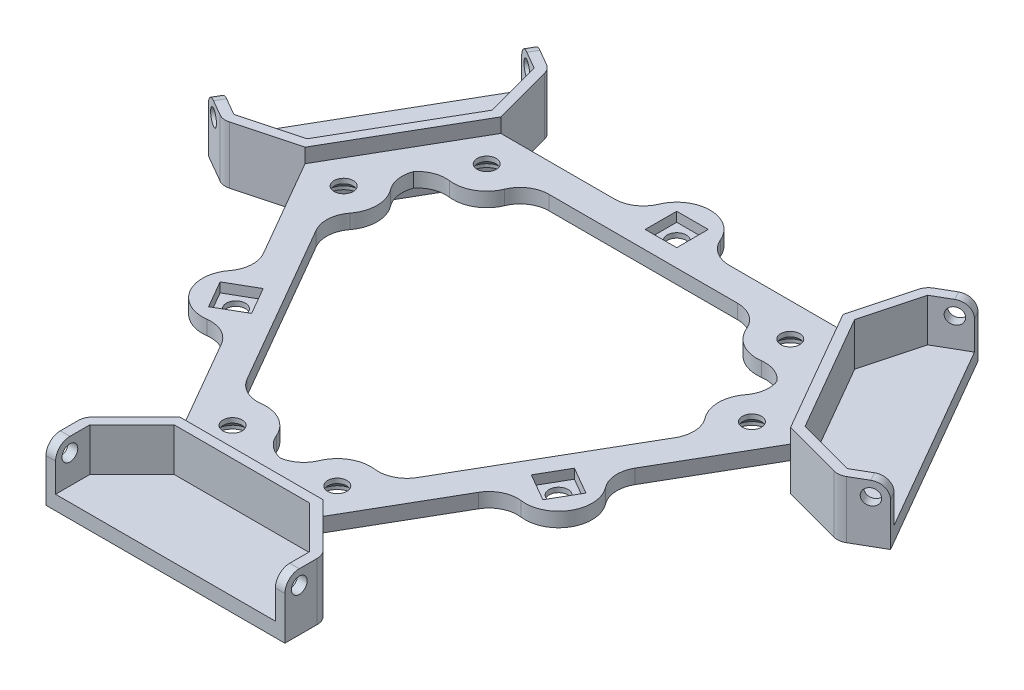
SolidWorks part; units mm, degrees
ref_plane "Front Plane" through (0, 0, 0) normal (0, 0, 1) x (1, 0, 0)
ref_plane "Top Plane" through (0, 0, 0) normal (0, 1, 0) x (1, 0, 0)
ref_plane "Right Plane" through (0, 0, 0) normal (1, 0, 0) x (0, 0, -1)
sketch "Sketch1" plane through (0, 0, 0) normal (0, 1, 0) x (1, 0, 0)
  line L0 (-55.8013, 3.3494) -> (-30.8013, 46.6506) construction
  line L1 (50.8013, 12.0096) -> (35.8013, 37.9904)
  line L2 (35.8013, 37.9904) -> (-35.8013, 37.9904)
  line L3 (-35.8013, 37.9904) -> (-50.8013, 12.0096)
  line L4 (-50.8013, 12.0096) -> (-15, -50)
  line L5 (-15, -50) -> (15, -50)
  line L6 (15, -50) -> (50.8013, 12.0096)
  line L7 (55.8013, 3.3494) -> (30.8013, 46.6506) construction
  line L8 (-25, -50) -> (25, -50) construction
  line L9 (-43.8731, 12.0096) -> (-11.5359, -44) construction
  line L10 (-11.5359, -44) -> (11.5359, -44) construction
  line L11 (11.5359, -44) -> (43.8731, 12.0096) construction
  line L12 (43.8731, 12.0096) -> (32.3372, 31.9904) construction
  line L13 (32.3372, 31.9904) -> (-32.3372, 31.9904) construction
  line L14 (-32.3372, 31.9904) -> (-43.8731, 12.0096) construction
  line L15 (-43.8731, 12.0096) -> (-50.8013, 12.0096) construction
  line L16 (-32.3372, 31.9904) -> (-35.8013, 37.9904) construction
  line L17 (32.3372, 31.9904) -> (35.8013, 37.9904) construction
  line L18 (43.8731, 12.0096) -> (50.8013, 12.0096) construction
  line L19 (11.5359, -44) -> (15, -50) construction
  line L20 (-11.5359, -44) -> (-15, -50) construction
  line L21 (-40.1203, 18.5096) -> (-36.0899, 25.4904)
  line L22 (24.8316, 31.9904) -> (-24.8316, 31.9904)
  line L23 (-40.1203, 5.5096) -> (-15.2887, -37.5)
  line L24 (-4.0303, -44) -> (4.0303, -44)
  line L25 (40.1203, 5.5096) -> (15.2887, -37.5)
  line L26 (40.1203, 18.5096) -> (36.0899, 25.4904)
  circle A0 centre (0, 0) radius 37.9904 construction
  circle A1 centre (0, 0) radius 50 construction
  arc A2 (-40.1203, 5.5096) -> (-40.1203, 18.5096) centre (-42.7184, 12.0096) ccw
  arc A3 (-36.0899, 25.4904) -> (-24.8316, 31.9904) centre (-31.7598, 30.9904) ccw
  arc A4 (24.8316, 31.9904) -> (36.0899, 25.4904) centre (31.7598, 30.9904) ccw
  arc A5 (40.1203, 18.5096) -> (40.1203, 5.5096) centre (42.7184, 12.0096) ccw
  arc A6 (15.2887, -37.5) -> (4.0303, -44) centre (10.9585, -43) ccw
  arc A7 (-4.0303, -44) -> (-15.2887, -37.5) centre (-10.9585, -43) ccw
  circle A8 centre (-42.7184, 12.0096) radius 7 construction
  point P13 (-43.3013, 25)
  point P16 (43.3013, 25)
  point P19 (0, -50)
  point P53 (0, 0)
  dimension "D4" = 3
  dimension "D5" = 14
  dimension "D6" = 100
  dimension "D1" = 50
  dimension "D2" = 10
  dimension "D3" = 6
extrude "Boss-Extrude1" add sketch "Sketch1" along normal blind 3
sketch "Sketch2" plane through (0, 0, 0) normal (0, -1, 0) x (1, 0, 0)
  line L0 (25, 68) -> (25, 60)
  line L1 (25, 60) -> (15, 50)
  line L2 (15, 50) -> (-15, 50)
  line L3 (-15, 50) -> (15, 50) construction
  line L4 (0, 50) -> (0, 52) construction
  line L5 (-14.1716, 52) -> (14.1716, 52)
  line L6 (14.1716, 52) -> (23, 60.8284)
  line L7 (-23, 60.8284) -> (-23, 68)
  line L8 (18.5858, 56.4142) -> (20, 55) construction
  line L9 (-23, 68) -> (-25, 68)
  line L10 (-18.5858, 56.4142) -> (-20, 55) construction
  line L11 (-25, 65) -> (25, 65) construction
  line L12 (-14.1716, 52) -> (-23, 60.8284)
  line L13 (-25, 60) -> (-15, 50)
  line L14 (-25, 68) -> (-25, 60)
  line L15 (23, 60.8284) -> (23, 68)
  line L16 (23, 68) -> (25, 68)
  dimension "D1" = 45
  dimension "D2" = 2
  dimension "D3" = 3
  dimension "D4" = 65
  dimension "D6" = 50
extrude "Boss-Extrude2" add sketch "Sketch2" against normal blind 6 and the other way blind 3
sketch "Sketch3" plane through (25, 0, 0) normal (1, 0, 0) x (0, 0, -1)
  line L0 (-68, 3) -> (-65, 3) construction
  line L2 (-60, 6) -> (-68, 6) construction
  circle A0 centre (-65, 3) radius 1.65
  dimension "D1" = 3.3
  dimension "D2" = 3
  dimension "D3" = 3
extrude "Cut-Extrude1" cut sketch "Sketch3" against normal through all
sketch "Sketch4" plane through (23, 0, 0) normal (1, 0, 0) x (0, 0, -1)
  line L1 (-61.1029, 3) -> (-63.0514, 6.375)
  line L2 (-63.0514, 6.375) -> (-66.9486, 6.375)
  line L3 (-66.9486, 6.375) -> (-68.8971, 3)
  line L4 (-68.8971, 3) -> (-66.9486, -0.375)
  line L5 (-66.9486, -0.375) -> (-63.0514, -0.375)
  line L6 (-63.0514, -0.375) -> (-61.1029, 3)
  circle A0 centre (-65, 3) radius 3.375 construction
  dimension "D1" = 6.75
extrude "Cut-Extrude2" [suppressed] cut sketch "Sketch4" against normal offset from surface 2 and the other way offset from surface 2
ref_axis "Axis1" through (0, 6.3, 0) along (0, -1, 0)
pattern_circular "CirPattern2" count 3 over 360 about axis through (0, 6.3, 0) along (0, -1, 0) of "Boss-Extrude2", "Cut-Extrude1"
sketch "Sketch6" plane through (-11.5, 0, -19.9186) normal (0.5, 0, 0.866) x (0.866, 0, -0.5)
  line L1 (61.1029, 3) -> (63.0514, -0.375)
  line L2 (63.0514, -0.375) -> (66.9486, -0.375)
  line L3 (66.9486, -0.375) -> (68.8971, 3)
  line L4 (68.8971, 3) -> (66.9486, 6.375)
  line L5 (66.9486, 6.375) -> (63.0514, 6.375)
  line L6 (63.0514, 6.375) -> (61.1029, 3)
  circle A0 centre (65, 3) radius 3.375 construction
  dimension "D1" = 6.75
extrude "Cut-Extrude4" [suppressed] cut sketch "Sketch6" against normal offset from surface 2 and the other way offset from surface 2
sketch "Sketch7" plane through (-11.5, 0, 19.9186) normal (0.5, 0, -0.866) x (-0.866, 0, -0.5)
  line L1 (61.1029, 3) -> (63.0514, -0.375)
  line L2 (63.0514, -0.375) -> (66.9486, -0.375)
  line L3 (66.9486, -0.375) -> (68.8971, 3)
  line L4 (68.8971, 3) -> (66.9486, 6.375)
  line L5 (66.9486, 6.375) -> (63.0514, 6.375)
  line L6 (63.0514, 6.375) -> (61.1029, 3)
  circle A0 centre (65, 3) radius 3.375 construction
  dimension "D1" = 6.75
extrude "Cut-Extrude5" [suppressed] cut sketch "Sketch7" against normal offset from surface 2 and the other way offset from surface 2
sketch "Sketch5" plane through (0, 3, 0) normal (0, 1, 0) x (1, 0, 0)
  circle A0 centre (42.7184, 12.0096) radius 2
  circle A1 centre (31.7598, 30.9904) radius 2
  circle A2 centre (10.9585, -43) radius 2
  circle A3 centre (-10.9585, -43) radius 2
  circle A4 centre (-42.7184, 12.0096) radius 2
  circle A5 centre (-31.7598, 30.9904) radius 2
  point P6 (0, 0)
  point P19 (0, 0)
  dimension "D1" = 4
  dimension "D2" = 3
extrude "Cut-Extrude3" cut sketch "Sketch5" against normal through all
fillet "Fillet2" radius 3 6 edges at (64.4615, 1.5, -8.3494) (39.4615, 1.5, -51.6506) (-39.4615, 1.5, -51.6506) (-64.4615, 1.5, -8.3494) (25, 1.5, 60) (-25, 1.5, 60)
sketch "Sketch8" plane through (0, 0, 0) normal (0, -1, 0) x (1, 0, 0)
  circle A0 centre (31.7598, -30.9904) radius 3.3
  circle A1 centre (42.7184, -12.0096) radius 3.3
  circle A2 centre (10.9585, 43) radius 3.3
  circle A3 centre (-10.9585, 43) radius 3.3
  circle A4 centre (-42.7184, -12.0096) radius 3.3
  circle A5 centre (-31.7598, -30.9904) radius 3.3
  dimension "D1" = 6.6
extrude "Cut-Extrude6" cut sketch "Sketch8" against normal blind 2
chamfer "Chamfer2" distance 1.3 angle 45 6 edges at (31.7598, 2, -34.2904) (42.7184, 2, -15.3096) (10.9585, 2, 39.7) (-10.9585, 2, 39.7) (-42.7184, 2, -15.3096) (-31.7598, 2, -34.2904)
sketch "Sketch9" plane through (0, 0, 0) normal (0, -1, 0) x (1, 0, 0)
  line L0 (-32.9006, 18.9952) -> (-33.7667, 19.4952) construction
  line L1 (-50.8013, -12.0096) -> (-15, 50) construction
  line L2 (-40.1203, -5.5096) -> (-15.2887, 37.5) construction
  line L3 (32.9006, 18.9952) -> (33.7667, 19.4952) construction
  line L4 (0, -37.9904) -> (0, -38.9904) construction
  circle A0 centre (-33.7667, 19.4952) radius 7
  circle A1 centre (33.7667, 19.4952) radius 7
  circle A2 centre (0, -38.9904) radius 7
  point P19 (0, 0)
  dimension "D1" = 14
  dimension "D2" = 3
extrude "Boss-Extrude3" add sketch "Sketch9" against normal up to surface (3 mm away) up to face at (-42.7184, 3, -10.0096)
sketch "Sketch10" plane through (0, 3, 0) normal (0, 1, 0) x (1, 0, 0)
  line L0 (32.5588, -14.9873) -> (29.2588, -20.7031)
  line L1 (-3.3, 35.6904) -> (3.3, 35.6904)
  line L2 (-3.3, 35.6904) -> (-3.3, 42.2904)
  line L3 (-3.3, 42.2904) -> (3.3, 42.2904)
  line L4 (3.3, 35.6904) -> (3.3, 42.2904)
  line L5 (-3.3, 35.6904) -> (3.3, 42.2904) construction
  line L6 (-3.3, 42.2904) -> (3.3, 35.6904) construction
  line L7 (32.5588, -14.9873) -> (38.2745, -18.2873)
  line L8 (38.2745, -18.2873) -> (34.9745, -24.0031)
  line L9 (29.2588, -20.7031) -> (34.9745, -24.0031)
  line L10 (32.5588, -14.9873) -> (34.9745, -24.0031) construction
  line L11 (38.2745, -18.2873) -> (29.2588, -20.7031) construction
  line L12 (-29.2588, -20.7031) -> (-32.5588, -14.9873)
  line L13 (-29.2588, -20.7031) -> (-34.9745, -24.0031)
  line L14 (-34.9745, -24.0031) -> (-38.2745, -18.2873)
  line L15 (-32.5588, -14.9873) -> (-38.2745, -18.2873)
  line L16 (-29.2588, -20.7031) -> (-38.2745, -18.2873) construction
  line L17 (-34.9745, -24.0031) -> (-32.5588, -14.9873) construction
  point P0 (0, 38.9904)
  point P8 (33.7667, -19.4952)
  point P13 (-33.7667, -19.4952)
  point P18 (0, 0)
  dimension "D1" = 6.6
  dimension "D2" = 3
extrude "Cut-Extrude7" cut sketch "Sketch10" against normal blind 2
sketch "Sketch11" plane through (0, 3, 0) normal (0, 1, 0) x (1, 0, 0)
  circle A0 centre (-33.7667, -19.4952) radius 2
  circle A1 centre (33.7667, -19.4952) radius 2
  circle A2 centre (0, 38.9904) radius 2
  dimension "D1" = 4
extrude "Cut-Extrude8" cut sketch "Sketch11" against normal through all
fillet "Fillet1" radius 6 18 edges at (-40.1203, 1.5, -18.5096) (-15.2887, 1.5, 37.5) (-4.0303, 1.5, 44) (4.0303, 1.5, 44) (15.2887, 1.5, 37.5) (40.1203, 1.5, -5.5096) (40.1203, 1.5, -18.5096) (36.0899, 1.5, -25.4904) (24.8316, 1.5, -31.9904) (-24.8316, 1.5, -31.9904) (-36.0899, 1.5, -25.4904) (-40.1203, 1.5, -5.5096) (-29.4365, 1.5, 24.9952) (29.4365, 1.5, 24.9952) (36.3647, 1.5, 12.9952) (-36.3647, 1.5, 12.9952) (-6.9282, 1.5, -37.9904) (6.9282, 1.5, -37.9904)
fillet "Fillet3" radius 3 6 edges at (-46.8897, 6, -54.7846) (-70.8897, 6, -13.2154) (24, 6, 68) (-24, 6, 68) (70.8897, 6, -13.2154) (46.8897, 6, -54.7846)
sketch "Sketch12" plane through (0, -3, 0) normal (0, -1, 0) x (1, 0, 0)
  line L0 (-23, 68) -> (23, 68)
  line L1 (70.3897, -14.0814) -> (47.3897, -53.9186)
  line L2 (-47.3897, -53.9186) -> (-70.3897, -14.0814)
  line L12 (71.3897, -12.3494) -> (65.5377, -8.9707)
  line L13 (63.2612, -8.671) -> (50.8013, -12.0096)
  line L14 (50.8013, -12.0096) -> (35.8013, -37.9904)
  line L15 (35.8013, -37.9904) -> (39.1399, -50.4503)
  line L16 (40.5377, -52.272) -> (46.3897, -55.6506)
  line L17 (46.3897, -55.6506) -> (47.3897, -53.9186)
  line L18 (47.3897, -53.9186) -> (41.179, -50.3328)
  line L19 (41.179, -50.3328) -> (37.9475, -38.2729)
  line L20 (37.9475, -38.2729) -> (52.1191, -13.7271)
  line L21 (52.1191, -13.7271) -> (64.179, -10.4956)
  line L22 (64.179, -10.4956) -> (70.3897, -14.0814)
  line L23 (70.3897, -14.0814) -> (71.3897, -12.3494)
  line L24 (71.3897, -12.3494) -> (65.5377, -8.9707)
  line L25 (63.2612, -8.671) -> (50.8013, -12.0096)
  line L26 (50.8013, -12.0096) -> (35.8013, -37.9904)
  line L27 (35.8013, -37.9904) -> (39.1399, -50.4503)
  line L28 (40.5377, -52.272) -> (46.3897, -55.6506)
  line L29 (46.3897, -55.6506) -> (47.3897, -53.9186)
  line L33 (-15, 50) -> (15, 50)
  line L34 (-15, 50) -> (15, 50)
  line L35 (70.3897, -14.0814) -> (71.3897, -12.3494)
  line L36 (15, 50) -> (24.1213, 59.1213)
  line L37 (25, 61.2426) -> (25, 68)
  line L38 (25, 68) -> (23, 68)
  line L39 (23, 68) -> (23, 60.8284)
  line L40 (23, 60.8284) -> (14.1716, 52)
  line L41 (14.1716, 52) -> (-14.1716, 52)
  line L42 (-14.1716, 52) -> (-23, 60.8284)
  line L43 (-23, 60.8284) -> (-23, 68)
  line L44 (-23, 68) -> (-25, 68)
  line L45 (-25, 68) -> (-25, 61.2426)
  line L46 (-24.1213, 59.1213) -> (-15, 50)
  line L48 (15, 50) -> (24.1213, 59.1213)
  line L49 (25, 61.2426) -> (25, 68)
  line L50 (25, 68) -> (23, 68)
  line L56 (-23, 68) -> (-25, 68)
  line L57 (-25, 68) -> (-25, 61.2426)
  line L58 (-24.1213, 59.1213) -> (-15, 50)
  line L72 (-46.3897, -55.6506) -> (-40.5377, -52.272)
  line L73 (-39.1399, -50.4503) -> (-35.8013, -37.9904)
  line L74 (-35.8013, -37.9904) -> (-50.8013, -12.0096)
  line L75 (-50.8013, -12.0096) -> (-63.2612, -8.671)
  line L76 (-65.5377, -8.9707) -> (-71.3897, -12.3494)
  line L77 (-71.3897, -12.3494) -> (-70.3897, -14.0814)
  line L83 (-47.3897, -53.9186) -> (-46.3897, -55.6506)
  arc A2 (65.5377, -8.9707) -> (63.2612, -8.671) centre (64.0377, -11.5688) ccw
  arc A3 (39.1399, -50.4503) -> (40.5377, -52.272) centre (42.0377, -49.6739) ccw
  arc A4 (65.5377, -8.9707) -> (63.2612, -8.671) centre (64.0377, -11.5688) ccw
  arc A5 (39.1399, -50.4503) -> (40.5377, -52.272) centre (42.0377, -49.6739) ccw
  arc A6 (24.1213, 59.1213) -> (25, 61.2426) centre (22, 61.2426) ccw
  arc A7 (-25, 61.2426) -> (-24.1213, 59.1213) centre (-22, 61.2426) ccw
  arc A8 (24.1213, 59.1213) -> (25, 61.2426) centre (22, 61.2426) ccw
  arc A9 (-25, 61.2426) -> (-24.1213, 59.1213) centre (-22, 61.2426) ccw
  arc A12 (-40.5377, -52.272) -> (-39.1399, -50.4503) centre (-42.0377, -49.6739) ccw
  arc A13 (-63.2612, -8.671) -> (-65.5377, -8.9707) centre (-64.0377, -11.5688) ccw
  dimension "D2" = 0
  dimension "D1" = 0
extrude "Boss-Extrude4" add sketch "Sketch12" along normal blind 3
